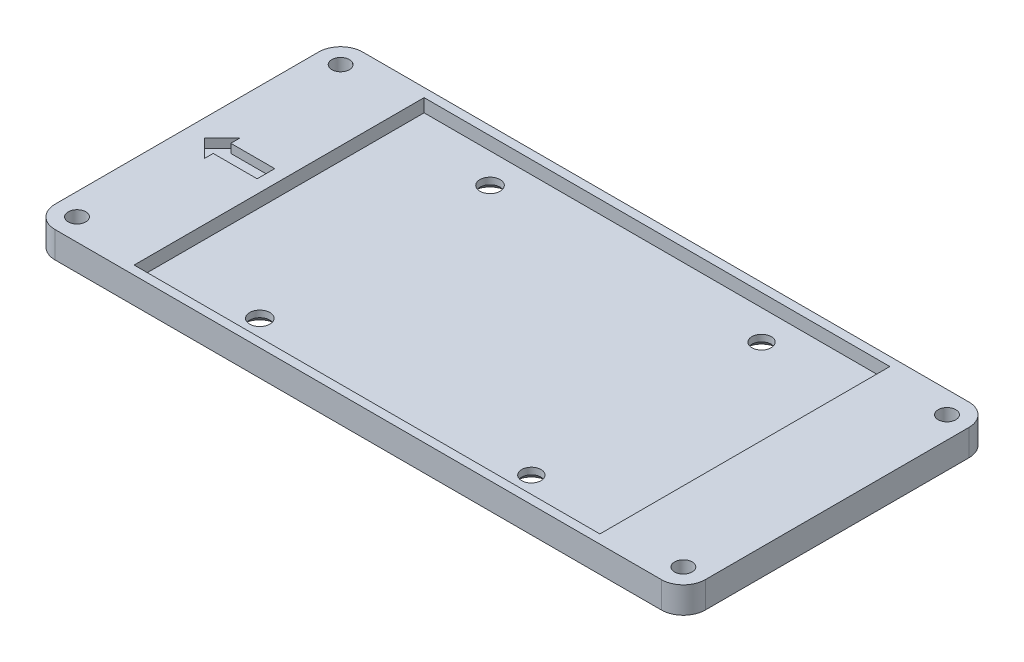
SolidWorks part; units mm, degrees
ref_plane "Płaszczyzna przednia" through (0, 0, 0) normal (0, 0, 1) x (1, 0, 0)
ref_plane "Płaszczyzna górna" through (0, 0, 0) normal (0, 1, 0) x (1, 0, 0)
ref_plane "Płaszczyzna prawa" through (0, 0, 0) normal (1, 0, 0) x (0, 0, -1)
sketch "Szkic1" plane through (0, 0, 0) normal (0, 1, 0) x (1, 0, 0)
  line L1 (-37, -17.5) -> (37, -17.5)
  line L2 (-37, -17.5) -> (-37, 17.5)
  line L3 (-37, 17.5) -> (37, 17.5)
  line L4 (37, -17.5) -> (37, 17.5)
  line L5 (-37, -17.5) -> (37, 17.5) construction
  line L6 (-37, 17.5) -> (37, -17.5) construction
  point P0 (0, 0)
  dimension "D1" = 74
  dimension "D2" = 35
extrude "Dodanie-wyciągnięcie1" add sketch "Szkic1" along normal blind 3
sketch "Szkic2" plane through (0, 3, 0) normal (0, 1, 0) x (1, 0, 0)
  line L1 (-26.5, -16.5) -> (26.5, -16.5)
  line L2 (-26.5, -16.5) -> (-26.5, 16.5)
  line L3 (-26.5, 16.5) -> (26.5, 16.5)
  line L4 (26.5, -16.5) -> (26.5, 16.5)
  line L5 (-26.5, -16.5) -> (26.5, 16.5) construction
  line L6 (-26.5, 16.5) -> (26.5, -16.5) construction
  point P0 (0, 0)
  dimension "D1" = 53
  dimension "D2" = 33
extrude "Wytnij-wyciągnięcie1" cut sketch "Szkic2" against normal blind 1.5
sketch "Szkic4" plane through (0, 3, 0) normal (0, 1, 0) x (1, 0, 0)
  line L0 (-37, 17.5) -> (-37, 15) construction
  line L1 (-37, 17.5) -> (-37, -17.5) construction
  line L2 (-37, 15) -> (-34.5, 15) construction
  circle A0 centre (-34.5, 15) radius 1
  dimension "D1" = 2
  dimension "D2" = 2.5
  dimension "D3" = 2.5
extrude "Wytnij-wyciągnięcie2" cut sketch "Szkic4" against normal through all
fillet "Zaokrąglenie1" radius 2.5 4 edges at (-37, 1.5, 17.5) (-37, 1.5, -17.5) (37, 1.5, -17.5) (37, 1.5, 17.5)
mirror "Lustro1" about plane through (0, 0, 0) normal (0, 0, 1) of "Wytnij-wyciągnięcie2"
mirror "Lustro2" about plane through (0, 0, 0) normal (1, 0, 0) of "Lustro1"
sketch "Szkic6" plane through (0, 1.5, 0) normal (0, 1, 0) x (1, 0, 0)
  line L0 (26.5, -16.5) -> (26.5, -13.1) construction
  line L1 (26.5, -16.5) -> (26.5, 16.5) construction
  line L2 (26.5, -13.1) -> (15.3, -13.1) construction
  line L3 (-26.5, -16.5) -> (-26.5, -13.1) construction
  line L4 (-26.5, 16.5) -> (-26.5, -16.5) construction
  line L5 (-26.5, -13.1) -> (-15.6, -13.1) construction
  circle A0 centre (-15.6, -13.1) radius 1.15
  circle A1 centre (15.3, -13.1) radius 1.1
  dimension "D5" = 2.3
  dimension "D6" = 2.2
  dimension "D1" = 3.4
  dimension "D2" = 11.2
  dimension "D3" = 10.9
  dimension "D4" = 3.4
extrude "Wytnij-wyciągnięcie3" cut sketch "Szkic6" against normal through all
chamfer "Sfazowanie1" distance 0.75 angle 45 2 edges at (15.3, 0, 14.2) (-15.6, 0, 14.25)
mirror "Lustro3" about plane through (0, 0, 0) normal (0, 0, 1) of "Wytnij-wyciągnięcie3", "Sfazowanie1"
sketch "Szkic7" plane through (0, 3, 0) normal (0, 1, 0) x (1, 0, 0)
  line L0 (-37, 0) -> (-35, 0) construction
  line L1 (-37, 15) -> (-37, -15) construction
  line L2 (-35, 0) -> (-33, 2)
  line L3 (-33, 2) -> (-33, 1)
  line L4 (-33, 1) -> (-28, 1)
  line L5 (-28, 1) -> (-28, -1)
  line L6 (-33, -1) -> (-28, -1)
  line L7 (-35, 0) -> (-33, -2)
  line L8 (-33, -2) -> (-33, -1)
  point P8 (-28, 0)
  point P11 (-28, 0)
  dimension "D1" = 2
  dimension "D2" = 2
  dimension "D3" = 135
  dimension "D4" = 1
  dimension "D5" = 5
extrude "Wytnij-wyciągnięcie4" cut sketch "Szkic7" against normal blind 1
